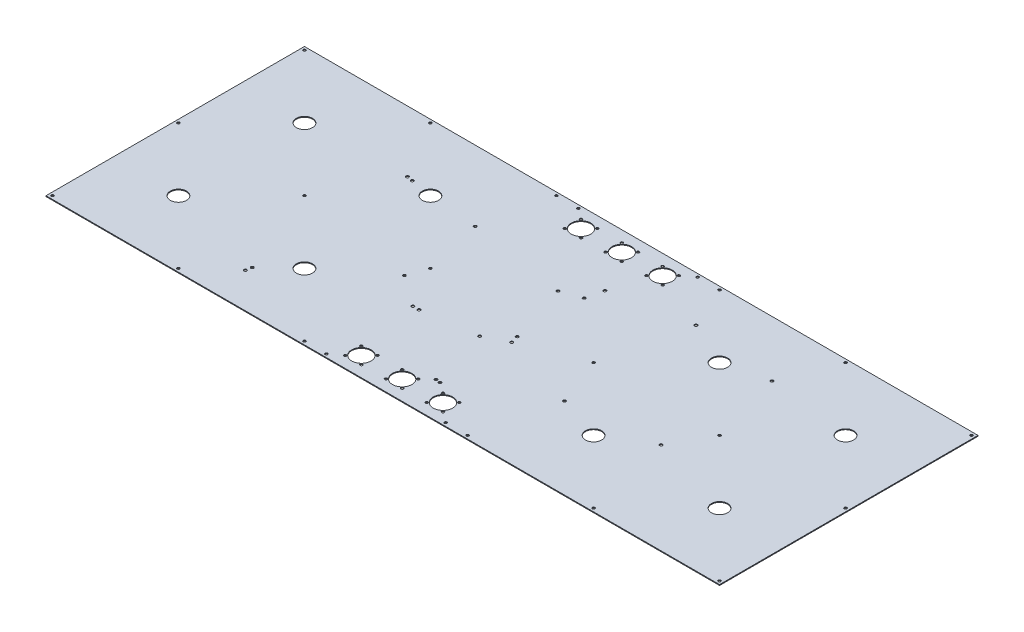
SolidWorks part; units mm, degrees
ref_plane "Front Plane" through (0, 0, 0) normal (0, 0, 1) x (1, 0, 0)
ref_plane "Top Plane" through (0, 0, 0) normal (0, 1, 0) x (1, 0, 0)
ref_plane "Right Plane" through (0, 0, 0) normal (1, 0, 0) x (0, 0, -1)
sketch "main_plate" plane through (0, 0, 0) normal (0, 1, 0) x (1, 0, 0)
  line L1 (-417, 160) -> (417, 160)
  line L2 (-417, 160) -> (-417, -160)
  line L3 (-417, -160) -> (417, -160)
  line L4 (417, 160) -> (417, -160)
  line L5 (-417, 160) -> (417, -160) construction
  line L6 (-417, -160) -> (417, 160) construction
  point P0 (0, 0)
  dimension "D1" = 320
  dimension "D2" = 834
extrude "Boss-Extrude1" add sketch "main_plate" along normal blind 1.016
sketch "main_holes" plane through (0, 1.016, 0) normal (0, 1, 0) x (1, 0, 0)
  line L0 (-417, 160) -> (-417, -160) construction
  line L1 (417, 160) -> (-417, 160) construction
  line L2 (-417, 0) -> (417, 0) construction
  line L3 (417, -160) -> (417, 160) construction
  line L4 (-417, -160) -> (417, -160) construction
  line L5 (0, 160) -> (0, -160) construction
  circle A0 centre (-413, 156) radius 1.6
  circle A6 centre (-257, 156) radius 1.6
  circle A7 centre (-101, 156) radius 1.6
  circle A8 centre (-257, 0) radius 1.6
  circle A9 centre (-101, 0) radius 1.6
  circle A10 centre (-257, -156) radius 1.6
  circle A11 centre (-101, -156) radius 1.6
  circle A12 centre (-413, 0) radius 1.6
  circle A13 centre (-413, -156) radius 1.6
  circle A18 centre (413, -156) radius 1.6
  circle A19 centre (413, 0) radius 1.6
  circle A20 centre (101, -156) radius 1.6
  circle A21 centre (257, -156) radius 1.6
  circle A22 centre (101, 0) radius 1.6
  circle A23 centre (257, 0) radius 1.6
  circle A24 centre (101, 156) radius 1.6
  circle A25 centre (257, 156) radius 1.6
  circle A28 centre (413, 156) radius 1.6
  circle A29 centre (-73.8188, 156) radius 1.6
  circle A31 centre (73.8188, 156) radius 1.6
  circle A32 centre (73.8188, -156) radius 1.6
  circle A33 centre (-73.8188, -156) radius 1.6
  dimension "D3" = 3.2
  dimension "D1" = 4
  dimension "D2" = 4
  dimension "D4" = 3
  dimension "D5" = 3
  dimension "D6" = 73.8188
extrude "Cut-Extrude1" cut sketch "main_holes" against normal through all
sketch "sma" plane through (0, 1.016, 0) normal (0, 1, 0) x (1, 0, 0)
  line L0 (0, 160) -> (0, -160) construction
  line L1 (417, 160) -> (-417, 160) construction
  line L2 (-417, -160) -> (417, -160) construction
  line L3 (-413, 156) -> (-257, 156) construction
  line L7 (-257, 0) -> (-413, 0) construction
  line L8 (-413, 0) -> (-413, 156) construction
  line L9 (-257, 156) -> (-257, 0) construction
  circle A0 centre (-335, 78) radius 10
  circle A1 centre (-179, 78) radius 10
  circle A2 centre (-179, -78) radius 10
  circle A3 centre (-335, -78) radius 10
  circle A4 centre (335, 78) radius 10
  circle A5 centre (179, 78) radius 10
  circle A6 centre (335, -78) radius 10
  circle A7 centre (179, -78) radius 10
  point P9 (-413, 78)
  point P10 (-335, 156)
  dimension "D1" = 20
  dimension "D2" = 2
  dimension "D3" = 2
extrude "Cut-Extrude2" cut sketch "sma" against normal through all
sketch "ads9+eval"
sketch_block_instance "Block9-1"
sketch_block "Block9"
sketch_block_instance "Block8-8"
sketch_block "Block8" parameters "D6"=3.2, "D1"=217.932, "D2"=70.358, "D3"=61.468, "D4"=193.04, "D5"=18.796, "D7"=81.28, "D8"=68.58, "D9"=94.71, "D10"=106.68
sketch_block_instance "Block7-4"
sketch_block "Block7" parameters "D3"=3.2, "D1"=215.9, "D2"=259.71, "D4"=6.48, "D5"=7.24, "D6"=111, "D7"=103.38, "D8"=18.04, "D9"=12.3976, "D10"=37.52, "D11"=11.13, "D12"=13.84, "D13"=110.43, "D14"=101.73, "D15"=7.74, "D16"=6.47, "D17"=37.51, "D18"=13.68, "D19"=8.76, "D20"=15.4, "D21"=8.22, "D22"=100.94, "D23"=7.02, "D24"=8.34, "D25"=18.41, "D26"=36.31, "D27"=27.78, "D28"=7.02, "D29"=8.22, "D30"=9.18, "D31"=73.31, "D32"=73.31, "D33"=82.56, "D34"=105.32, "D35"=95.85
extrude "selective_holes" [suppressed] cut sketch "ads9+eval" against normal through all
sketch "ads9+eval_2" plane through (0, 1.016, 1.016) normal (0, 1, 0) x (1, 0, 0)
  line L0 (-220.0456, 92.198) -> (39.6644, 92.198) construction
  line L1 (-220.0456, 92.198) -> (-220.0456, -123.702) construction
  line L2 (-220.0456, -123.702) -> (39.6644, -123.702) construction
  line L3 (39.6644, 92.198) -> (39.6644, -123.702) construction
  line L4 (-220.0456, 92.198) -> (39.6644, -123.702) construction
  line L5 (-220.0456, -123.702) -> (39.6644, 92.198) construction
  line L6 (10.848, 23.305) -> (247.576, 23.178) construction
  line L7 (29.644, 119.698) -> (247.576, 119.698) construction
  line L8 (29.644, 119.698) -> (29.644, 58.484) construction
  line L9 (29.644, -73.342) -> (247.576, -73.342) construction
  line L10 (247.576, 119.698) -> (247.576, -73.342) construction
  line L11 (29.644, 119.698) -> (247.576, -73.342) construction
  line L12 (29.644, -73.342) -> (247.576, 119.698) construction
  line L13 (10.848, 58.484) -> (29.644, 58.484) construction
  line L14 (10.848, 58.484) -> (10.848, -11.874) construction
  line L15 (10.848, -11.874) -> (29.644, -11.874) construction
  line L16 (29.644, -73.342) -> (29.644, -11.874) construction
  circle A0 centre (-213.5656, 85.178) radius 1.75
  circle A1 centre (-206.3256, 83.858) radius 1.75
  circle A2 centre (-212.3056, -108.302) radius 1.75
  circle A3 centre (-213.5756, -115.482) radius 1.75
  circle A4 centre (-71.3356, -50.392) radius 1.75
  circle A5 centre (-63.7156, -50.392) radius 1.75
  circle A6 centre (2.1444, -41.142) radius 1.75
  circle A7 centre (-109.6156, -22.762) radius 1.75
  circle A8 centre (28.5344, -27.852) radius 1.75
  circle A9 centre (25.8244, -18.382) radius 1.75
  circle A10 centre (21.6244, -114.522) radius 1.75
  circle A11 centre (27.2668, -115.482) radius 1.75
  circle A12 centre (2.1544, 55.888) radius 1.75
  circle A13 centre (25.9844, 64.418) radius 1.75
  circle A14 centre (30.9044, 85.178) radius 1.75
  circle A15 centre (-118.3156, 73.788) radius 1.75
  circle A16 centre (124.354, 104.5241) radius 1.75
  circle A17 centre (231.034, 91.7669) radius 1.75
  circle A18 centre (230.9604, -45.3931) radius 1.75
  circle A19 centre (124.2668, -58.0358) radius 1.75
  point P0 (-90.1906, -15.752)
  point P37 (138.61, 23.178)
  dimension "D6" = 3.5
  dimension "D44" = 3.5
  dimension "D1" = 27.5
  dimension "D2" = 97
  dimension "D3" = 100.3781
  dimension "D4" = 215.9
  dimension "D5" = 259.71
  dimension "D7" = 6.48
  dimension "D8" = 7.24
  dimension "D9" = 111
  dimension "D10" = 103.38
  dimension "D11" = 18.04
  dimension "D12" = 12.3976
  dimension "D13" = 37.52
  dimension "D14" = 11.13
  dimension "D15" = 13.84
  dimension "D16" = 110.43
  dimension "D17" = 101.73
  dimension "D18" = 7.74
  dimension "D19" = 6.47
  dimension "D20" = 37.51
  dimension "D21" = 13.68
  dimension "D22" = 8.76
  dimension "D23" = 15.4
  dimension "D24" = 8.22
  dimension "D25" = 100.94
  dimension "D26" = 7.02
  dimension "D27" = 8.34
  dimension "D28" = 18.41
  dimension "D29" = 36.31
  dimension "D30" = 27.78
  dimension "D31" = 7.02
  dimension "D32" = 8.22
  dimension "D33" = 9.18
  dimension "D34" = 73.31
  dimension "D35" = 73.31
  dimension "D36" = 82.56
  dimension "D37" = 105.32
  dimension "D38" = 95.85
  dimension "D39" = 217.932
  dimension "D40" = 70.358
  dimension "D41" = 61.468
  dimension "D42" = 193.04
  dimension "D43" = 18.796
  dimension "D45" = 81.28
  dimension "D46" = 68.58
  dimension "D47" = 94.71
  dimension "D48" = 106.68
extrude "full_holes" cut sketch "ads9+eval_2" against normal through all
sketch "fan" plane through (0, 1.016, -2.032) normal (0, -1, 0) x (1, 0, 0)
  line L0 (417, -157.968) -> (-417, -157.968) construction
  line L1 (-417, 162.032) -> (417, 162.032) construction
  circle B0 centre (-10, -123.968) radius 1.6
  circle B1 centre (10, -123.968) radius 1.6
  circle B2 centre (10, -143.968) radius 1.6
  circle B3 centre (-10, -143.968) radius 1.6
  circle B4 centre (0, -133.968) radius 12
  circle B5 centre (-60.5, -123.968) radius 1.6
  circle B6 centre (-40.5, -123.968) radius 1.6
  circle B7 centre (-40.5, -143.968) radius 1.6
  circle B8 centre (-60.5, -143.968) radius 1.6
  circle B9 centre (-50.5, -133.968) radius 12
  circle B10 centre (40.5, -123.968) radius 1.6
  circle B11 centre (60.5, -123.968) radius 1.6
  circle B12 centre (60.5, -143.968) radius 1.6
  circle B13 centre (40.5, -143.968) radius 1.6
  circle B14 centre (50.5, -133.968) radius 12
  circle B15 centre (-10, -144.984) radius 1.6
  circle B16 centre (10, -144.984) radius 1.6
  circle B17 centre (10, -164.984) radius 1.6
  circle B18 centre (-10, -164.984) radius 1.6
  circle B19 centre (0, -154.984) radius 12
  circle B20 centre (-10, 148.032) radius 1.6
  circle B21 centre (10, 148.032) radius 1.6
  circle B22 centre (10, 128.032) radius 1.6
  circle B23 centre (-10, 128.032) radius 1.6
  circle B24 centre (0, 138.032) radius 12
  circle B25 centre (-60.5, 148.032) radius 1.6
  circle B26 centre (-40.5, 148.032) radius 1.6
  circle B27 centre (-40.5, 128.032) radius 1.6
  circle B28 centre (-60.5, 128.032) radius 1.6
  circle B29 centre (-50.5, 138.032) radius 12
  circle B30 centre (40.5, 148.032) radius 1.6
  circle B31 centre (60.5, 148.032) radius 1.6
  circle B32 centre (60.5, 128.032) radius 1.6
  circle B33 centre (40.5, 128.032) radius 1.6
  circle B34 centre (50.5, 138.032) radius 12
  dimension "D1" = 24
  dimension "D2" = 24
sketch_block_instance "Block13-1"
sketch_block "Block13"
sketch_block_instance "Block2-13"
sketch_block "Block2" parameters "D1"=3.2, "D2"=24, "D3"=10, "D4"=10, "D5"=10, "D6"=10
sketch_block_instance "Block2-14"
sketch_block_instance "Block2-15"
sketch_block_instance "Block2-16"
sketch_block_instance "Block13-2"
extrude "Cut-Extrude4" cut sketch "fan" along normal through all
